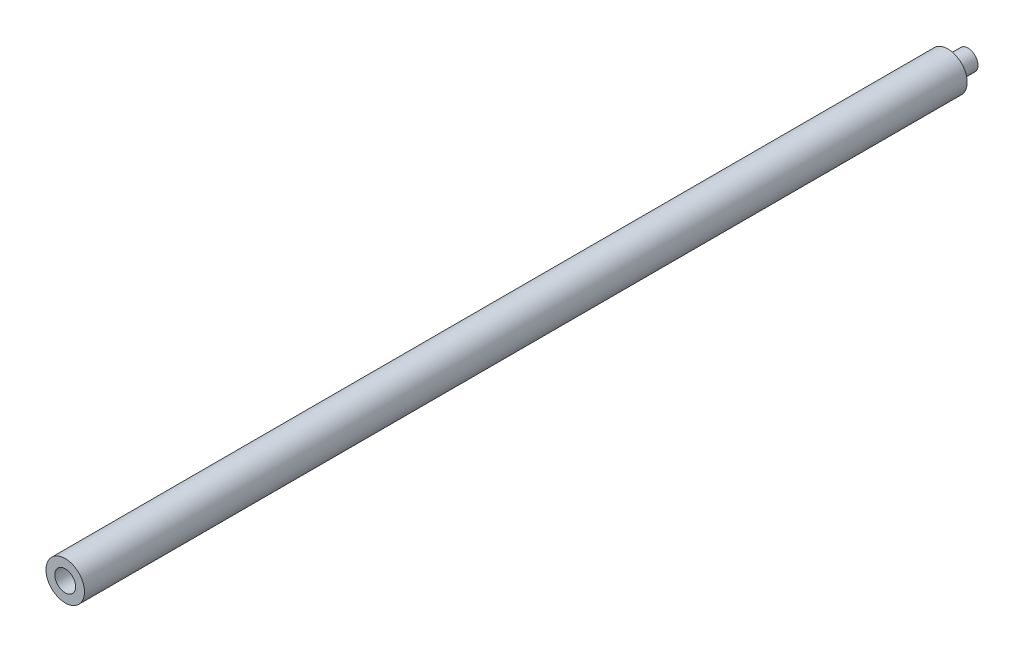
SolidWorks part; units mm, degrees
ref_plane "Front Plane" through (0, 0, 0) normal (0, 0, 1) x (1, 0, 0)
ref_plane "Top Plane" through (0, 0, 0) normal (0, 1, 0) x (1, 0, 0)
ref_plane "Right Plane" through (0, 0, 0) normal (1, 0, 0) x (0, 0, -1)
sketch "Sketch1" plane through (0, 0, 0) normal (0, 0, 1) x (1, 0, 0)
  line L0 (0, -2.4) -> (0, 2.4) construction
  circle A0 centre (0, 0) radius 2.4
  point P6 (0, 0)
  dimension "D2" = 4.8
extrude "Boss-Extrude1" add sketch "Sketch1" along normal blind 110
sketch "Sketch6" plane through (0, 0, 0) normal (0, 0, -1) x (-1, 0, 0)
  circle A0 centre (0, 0) radius 1.25
  dimension "D1" = 2.5
extrude "Boss-Extrude2" add sketch "Sketch6" along normal blind 2.5
sketch "Sketch7" plane through (0, 0, 110) normal (0, 0, 1) x (1, 0, 0)
  circle A0 centre (0, 0) radius 1.3
  dimension "D1" = 2.6
extrude "Cut-Extrude1" cut sketch "Sketch7" against normal blind 2.5
